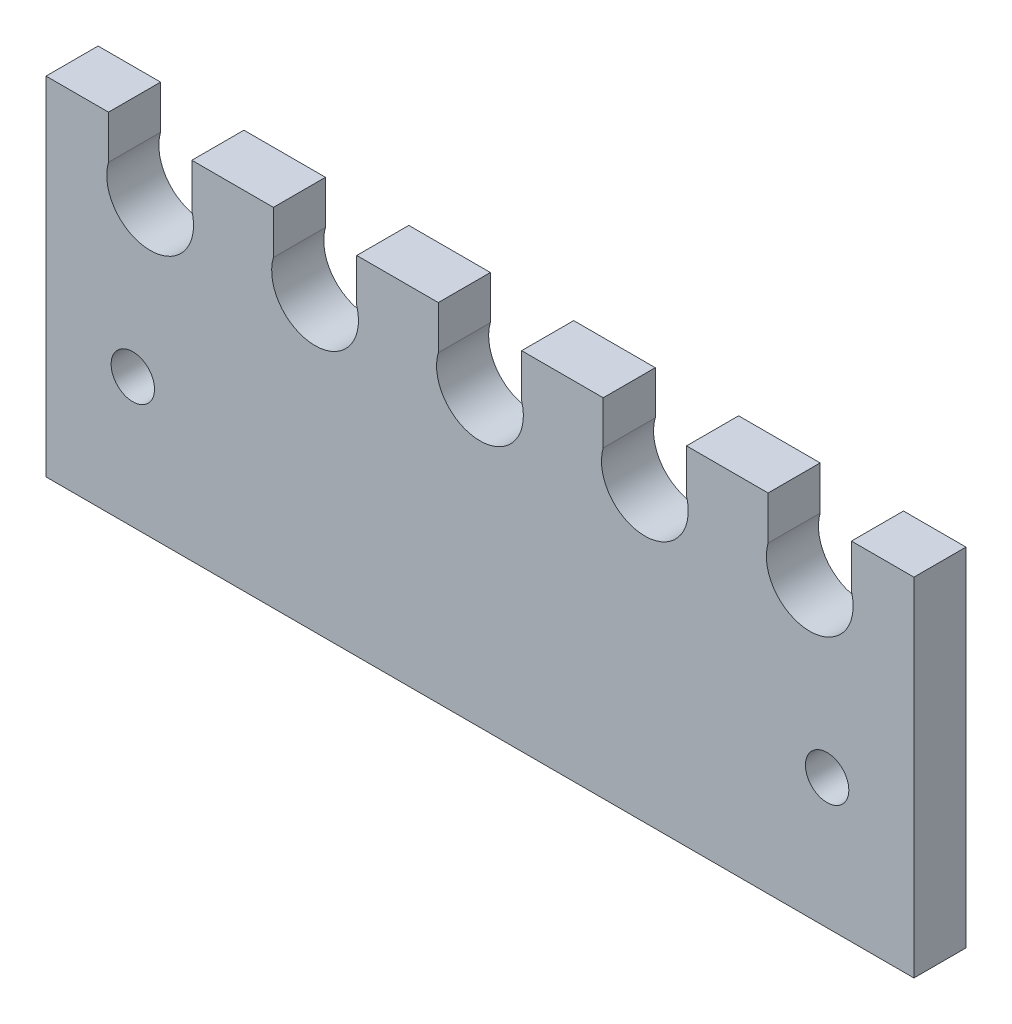
SolidWorks part; units mm, degrees
material "Sapin"
ref_plane "Plan de face" through (0, 0, 0) normal (0, 0, 1) x (1, 0, 0)
ref_plane "Plan de dessus" through (0, 0, 0) normal (0, 1, 0) x (1, 0, 0)
ref_plane "Plan de droite" through (0, 0, 0) normal (1, 0, 0) x (0, 0, -1)
sketch "Esquisse1" plane through (0, 0, 0) normal (0, 0, 1) x (1, 0, 0)
  line L1 (-50, -20) -> (50, -20)
  line L2 (-50, -20) -> (-50, 20)
  line L3 (-50, 20) -> (50, 20)
  line L4 (50, -20) -> (50, 20)
  line L5 (-50, -20) -> (50, 20) construction
  line L6 (-50, 20) -> (50, -20) construction
  point P0 (0, 0)
  dimension "D1" = 100
  dimension "D2" = 40
extrude "Boss.-Extru.1" add sketch "Esquisse1" along normal blind 6
sketch "Esquisse2" plane through (0, 0, 6) normal (0, 0, 1) x (1, 0, 0)
  line L0 (-42.8, 15) -> (-42.8, 20)
  line L1 (50, 20) -> (-50, 20) construction
  line L2 (-42.8, 20) -> (-33.2, 20)
  line L3 (-33.2, 20) -> (-33.2, 15)
  line L4 (-50, 20) -> (-50, -20) construction
  line L5 (-23.8, 15) -> (-23.8, 20)
  line L6 (-23.8, 20) -> (-14.2, 20)
  line L7 (-14.2, 20) -> (-14.2, 15)
  line L8 (-4.8, 15) -> (-4.8, 20)
  line L9 (-4.8, 20) -> (4.8, 20)
  line L10 (4.8, 20) -> (4.8, 15)
  line L11 (14.2, 15) -> (14.2, 20)
  line L12 (14.2, 20) -> (23.8, 20)
  line L13 (23.8, 20) -> (23.8, 15)
  line L14 (33.2, 15) -> (33.2, 20)
  line L15 (33.2, 20) -> (42.8, 20)
  line L16 (42.8, 20) -> (42.8, 15)
  line L17 (50, -20) -> (50, 20) construction
  arc A0 (-42.8, 15) -> (-33.2, 15) centre (-38, 13.6) ccw
  arc A1 (-23.8, 15) -> (-14.2, 15) centre (-19, 13.6) ccw
  arc A2 (-4.8, 15) -> (4.8, 15) centre (0, 13.6) ccw
  arc A3 (14.2, 15) -> (23.8, 15) centre (19, 13.6) ccw
  arc A4 (33.2, 15) -> (42.8, 15) centre (38, 13.6) ccw
  point P3 (0, 13.6)
  dimension "D2" = 5
  dimension "D1" = 9.6
  dimension "D3" = 5
  dimension "D4" = 12
  dimension "D6" = 12
  dimension "D5" = 5
extrude "Enlèv. mat.-Extru.1" cut sketch "Esquisse2" against normal through all
sketch "Esquisse3" plane through (0, 0, 6) normal (0, 0, 1) x (1, 0, 0)
  line L0 (-40, -5) -> (40, -5) construction
  line L5 (-50, -20) -> (50, -20) construction
  circle A0 centre (-40, -5) radius 2.5
  circle A1 centre (40, -5) radius 2.5
  point P4 (0, -5)
  dimension "D2" = 5
  dimension "D1" = 80
  dimension "D3" = 15
extrude "Enlèv. mat.-Extru.2" cut sketch "Esquisse3" against normal through all
